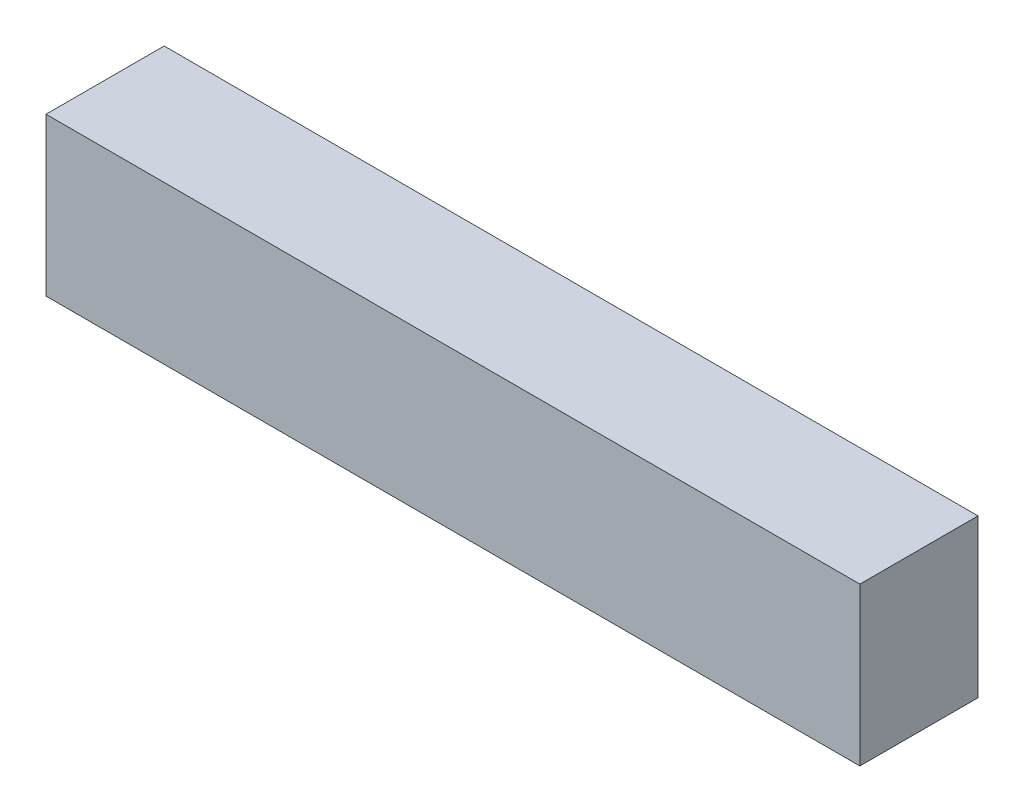
SolidWorks part; units mm, degrees
ref_plane "Front Plane" through (0, 0, 0) normal (0, 0, 1) x (1, 0, 0)
ref_plane "Top Plane" through (0, 0, 0) normal (0, 1, 0) x (1, 0, 0)
ref_plane "Right Plane" through (0, 0, 0) normal (1, 0, 0) x (0, 0, -1)
other "Configuration Table"
sketch "Sketch1" plane through (0, 0, 0) normal (0, 0, 1) x (1, 0, 0)
  line L0 (300, 150) -> (4400, 150)
  line L1 (4400, 150) -> (4400, 1126.9539)
  line L2 (4400, 1126.9539) -> (3600, 1500)
  line L3 (3600, 1500) -> (300, 1500)
  line L4 (0, 1200) -> (0, 450)
  arc A0 (300, 1500) -> (0, 1200) centre (300, 1200) ccw
  arc A1 (0, 450) -> (300, 150) centre (300, 450) ccw
extrude "car_body" add sketch "Sketch1" along normal blind 900 separate body
sketch "Sketch2" plane through (0, 0, 0) normal (1, 0, 0) x (0, 0, -1)
  line L1 (10, 470) -> (-225, 470)
  line L2 (10, 470) -> (10, 820)
  line L3 (10, 820) -> (-225, 820)
  line L4 (-225, 470) -> (-225, 820)
  line L5 (10, 470) -> (-225, 820) construction
  line L6 (10, 820) -> (-225, 470) construction
extrude "grille_duct" add sketch "Sketch2" along normal blind 500 from offset 50 separate body offset against normal yes
combine bodies "Combine1" operation type subtract main body 102 bodies to subtract 103
sketch "Sketch3" plane through (0, 0, 0) normal (1, 0, 0) x (0, 0, -1)
  line L1 (10, 100) -> (-225, 100)
  line L2 (10, 100) -> (10, 475)
  line L3 (10, 475) -> (-225, 475)
  line L4 (-225, 100) -> (-225, 475)
  line L5 (10, 100) -> (-225, 475) construction
  line L6 (10, 475) -> (-225, 100) construction
extrude "floor_exit" add sketch "Sketch3" along normal blind 150 from offset 300 separate body
combine bodies "Combine2" operation type subtract main body 104 bodies to subtract 105
sketch "Sketch4" plane through (0, 0, 0) normal (1, 0, 0) x (0, 0, -1)
  line L1 (0, 470) -> (-225, 470)
  line L2 (0, 470) -> (0, 820)
  line L3 (0, 820) -> (-225, 820)
  line L4 (-225, 470) -> (-225, 820)
  line L5 (0, 470) -> (-225, 820) construction
  line L6 (0, 820) -> (-225, 470) construction
extrude "radiator" add sketch "Sketch4" along normal blind 25 from offset 200 separate body
sketch "Sketch5" plane through (0, 0, 0) normal (1, 0, 0) x (0, 0, -1)
  line L1 (0, 470) -> (-225, 470)
  line L2 (0, 470) -> (0, 820)
  line L3 (0, 820) -> (-225, 820)
  line L4 (-225, 470) -> (-225, 820)
  line L5 (0, 470) -> (-225, 820) construction
  line L6 (0, 820) -> (-225, 470) construction
extrude "radiator_tool" add sketch "Sketch5" along normal blind 25 from offset 200 separate body
sketch "Sketch6" plane through (0, 0, 0) normal (1, 0, 0) x (0, 0, -1)
  line L1 (0, 0) -> (-4500, 0)
  line L2 (0, 0) -> (0, 6000)
  line L3 (0, 6000) -> (-4500, 6000)
  line L4 (-4500, 0) -> (-4500, 6000)
  line L5 (0, 0) -> (-4500, 6000) construction
  line L6 (0, 6000) -> (-4500, 0) construction
extrude "fluid_domain" add sketch "Sketch6" along normal blind 31000 from offset 9000 separate body offset against normal yes
combine bodies "Combine3" operation type subtract main body 109 bodies to subtract 106
combine bodies "Combine4" operation type subtract main body 110 bodies to subtract 108
